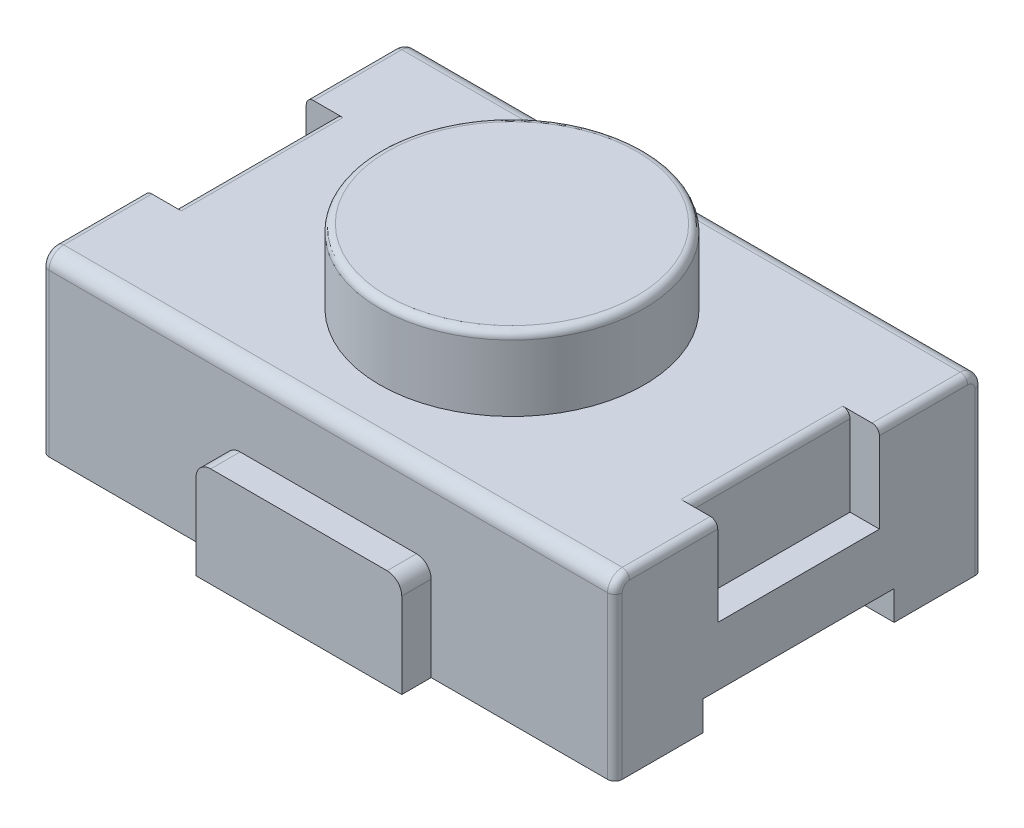
SolidWorks part; units mm, degrees
ref_plane "前视基准面" through (0, 0, 0) normal (0, 0, 1) x (1, 0, 0)
ref_plane "上视基准面" through (0, 0, 0) normal (0, 1, 0) x (1, 0, 0)
ref_plane "右视基准面" through (0, 0, 0) normal (1, 0, 0) x (0, 0, -1)
sketch "草图1" plane through (0, 0, 0) normal (0, 1, 0) x (1, 0, 0)
  line L0 (-2.5, 0) -> (2.5, 0) construction
  line L1 (0, 2) -> (0, -2) construction
  line L3 (-1.95, 1.25) -> (1.95, 1.25)
  line L4 (-1.95, 1.25) -> (-1.95, -1.25)
  line L5 (-1.95, -1.25) -> (1.95, -1.25)
  line L6 (1.95, 1.25) -> (1.95, -1.25)
  line L7 (-1.95, 1.25) -> (1.95, -1.25) construction
  line L8 (-1.95, -1.25) -> (1.95, 1.25) construction
  point P0 (0, 0)
  point P4 (0, 0)
  point P8 (0, 0)
  dimension "D1" = 3.9
  dimension "D2" = 2.5
extrude "凸台-拉伸1" add sketch "草图1" against normal blind 1.2
sketch "草图2" plane through (0, 0, 0) normal (0, 1, 0) x (1, 0, 0)
  line L0 (-2.3495, 0) -> (2.3495, 0) construction
  line L1 (0, 1.6415) -> (0, -1.6415) construction
  circle A0 centre (0, 0) radius 0.9
  point P4 (0, 0)
  point P8 (0, 0)
extrude "凸台-拉伸2" add sketch "草图2" along normal blind 0.5
sketch "草图3" plane through (0, 0, 1.25) normal (0, 0, 1) x (1, 0, 0)
  line L0 (0, 1.6768) -> (0, -1.6768) construction
  line L2 (-2.5791, 0) -> (2.5791, 0) construction
  line L3 (-0.6, -0.52) -> (0.6, -0.52)
  line L4 (0.7, -0.62) -> (0.7, -1.2)
  line L5 (-1.95, -1.2) -> (1.95, -1.2) construction
  line L6 (0.7, -1.2) -> (-0.7, -1.2)
  line L7 (-0.7, -1.2) -> (-0.7, -0.62)
  arc A0 (-0.6, -0.52) -> (-0.7, -0.62) centre (-0.6, -0.62) ccw
  arc A1 (0.7, -0.62) -> (0.6, -0.52) centre (0.6, -0.62) ccw
  point P4 (0, 0)
  point P8 (0, 0)
  point P11 (0, -0.52)
  point P16 (-0.7, -0.52)
  point P19 (0.7, -0.52)
  dimension "D3" = 0.1
  dimension "D1" = 0.52
  dimension "D2" = 1.4
extrude "凸台-拉伸3" add sketch "草图3" along normal blind 0.2
mirror "镜向1" about plane through (0, 0, 0) normal (0, 0, 1) of "凸台-拉伸3"
sketch "草图4" plane through (1.95, 0, 0) normal (1, 0, 0) x (0, 0, -1)
  line L0 (0, 1.6765) -> (0, -1.6765) construction
  line L1 (-1.6939, 0) -> (1.6939, 0) construction
  line L2 (-0.55, -0.6) -> (0.55, -0.6)
  line L3 (-0.55, -0.6) -> (-0.55, 0)
  line L4 (-0.55, 0) -> (0.55, 0)
  line L5 (0.55, 0) -> (0.55, -0.6)
  point P4 (0, 0)
  point P8 (0, 0)
  point P11 (0, -0.6)
  dimension "D1" = 0.6
  dimension "D2" = 1.1
extrude "切除-拉伸1" cut sketch "草图4" against normal blind 0.2
mirror "镜向2" about plane through (0, 0, 0) normal (1, 0, 0) of "切除-拉伸1"
fillet "圆角1" radius 0.1 2 edges at (0, 0, 1.25) (0, 0, -1.25)
sketch "草图5" plane through (0, -1.2, 0) normal (0, -1, 0) x (1, 0, 0)
  line L0 (-2.3731, 0) -> (2.3731, 0) construction
  line L1 (0, 1.6649) -> (0, -1.6649) construction
  line L2 (-1.95, -1.25) -> (-1.95, 1.25) construction
  line L3 (-2.45, 0.65) -> (-1.45, 0.65)
  line L4 (-2.45, 0.65) -> (-2.45, -0.65)
  line L5 (-2.45, -0.65) -> (-1.45, -0.65)
  line L6 (-1.45, 0.65) -> (-1.45, -0.65)
  line L7 (-2.45, 0.65) -> (-1.45, -0.65) construction
  line L8 (-2.45, -0.65) -> (-1.45, 0.65) construction
  point P0 (-1.95, 0)
  point P4 (0, 0)
  point P8 (0, 0)
  dimension "D1" = 1
  dimension "D2" = 1.3
extrude "切除-拉伸2" cut sketch "草图5" against normal blind 0.2
mirror "镜向3" about plane through (0, 0, 0) normal (1, 0, 0) of "切除-拉伸2"
sketch "草图6" plane through (0, -1.2, 0) normal (0, -1, 0) x (-1, 0, 0)
  line L0 (1.3094, 0) -> (-1.3094, 0) construction
  text T0 "Designed by Jarvis" font "Consolas" height 0.1
  point P4 (0, 0)
extrude "切除-拉伸3" cut sketch "草图6" against normal blind 0.01
fillet "圆角2" radius 0.05 1 edges at (0, 0.5, 0.9)
fillet "圆角4" radius 0.05 12 edges at (-1.95, 0, -0.85) (-1.95, -0.0293, -1.2207) (-1.95, 0, 0.85) (-1.95, -0.0293, 1.2207) (1.95, 0, 0.85) (1.95, -0.0293, 1.2207) (1.95, 0, -0.85) (1.95, -0.0293, -1.2207) (-1.95, -0.65, -1.25) (-1.95, -0.65, 1.25) (1.95, -0.65, 1.25) (1.95, -0.65, -1.25)
fillet "圆角5" radius 0.05 2 edges at (1.75, 0, 0) (-1.75, 0, 0)
